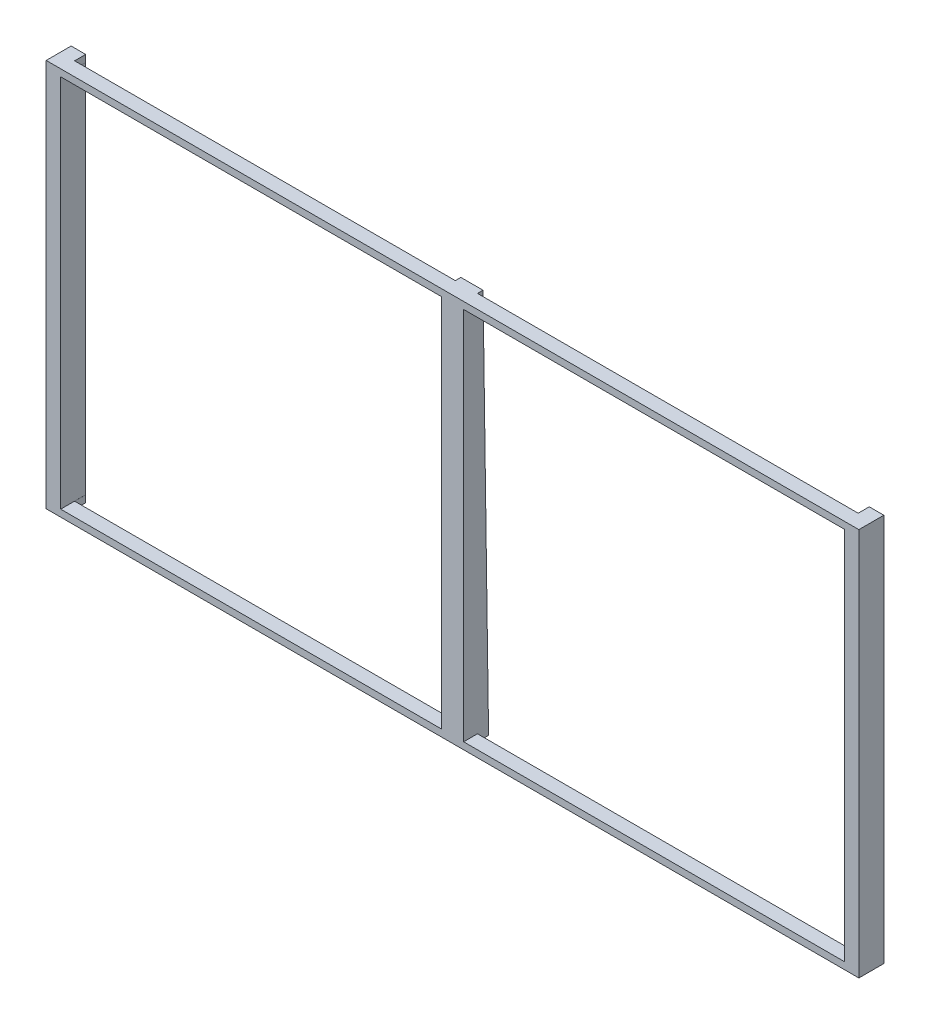
SolidWorks part; units mm, degrees
ref_plane "Спереди" through (0, 0, 0) normal (0, 0, 1) x (1, 0, 0)
ref_plane "Сверху" through (0, 0, 0) normal (0, 1, 0) x (1, 0, 0)
ref_plane "Справа" through (0, 0, 0) normal (1, 0, 0) x (0, 0, -1)
sketch "Эскиз1" plane through (0, 0, 0) normal (0, 0, 1) x (1, 0, 0)
  line L1 (-2930, 1400) -> (2930, 1400)
  line L2 (-2930, 1400) -> (-2930, -1400)
  line L3 (-2930, -1400) -> (2930, -1400)
  line L4 (2930, 1400) -> (2930, -1400)
  line L5 (-2930, 1400) -> (2930, -1400) construction
  line L6 (-2930, -1400) -> (2930, 1400) construction
  line L7 (-2825.3571, 1350) -> (-80, 1350)
  line L8 (-2825.3571, 1350) -> (-2825.3571, -1350)
  line L9 (-2825.3571, -1350) -> (-80, -1350)
  line L10 (-80, 1350) -> (-80, -1350)
  line L11 (80, 1350) -> (2825.3571, 1350)
  line L12 (80, 1350) -> (80, -1350)
  line L13 (80, -1350) -> (2825.3571, -1350)
  line L14 (2825.3571, 1350) -> (2825.3571, -1350)
  point P0 (0, 0)
extrude "Бобышка-Вытянуть1" add sketch "Эскиз1" along normal blind 180
sketch "Эскиз2" plane through (0, -1400, 0) normal (0, -1, 0) x (1, 0, 0)
  line L2 (-2825, 80) -> (-80, 80)
  line L3 (-2825, 80) -> (-2825, 0)
  line L4 (-2825, 0) -> (-80, 0)
  line L5 (-80, 80) -> (-80, 0)
  line L6 (-2825, 80) -> (-80, 0) construction
  line L7 (-2825, 0) -> (-80, 80) construction
  line L8 (0, 424.0898) -> (0, -233.7336) construction
  line L9 (2825, 0) -> (80, 80) construction
  line L10 (2825, 80) -> (80, 0) construction
  line L11 (80, 80) -> (80, 0)
  line L12 (2825, 0) -> (80, 0)
  line L13 (2825, 80) -> (2825, 0)
  line L14 (2825, 80) -> (80, 80)
  line L15 (-2930, 0) -> (2930, 0) construction
  point P2 (-1452.5, 40)
  point P15 (1452.5, 40)
extrude "Вырез-Вытянуть1" cut sketch "Эскиз2" against normal through all
sketch "Эскиз3" plane through (-80, 0, 0) normal (-1, 0, 0) x (0, 0, 1)
  line L0 (0, 1400) -> (0, -1400)
  line L1 (0, 1400) -> (80, 1400) construction
  line L2 (0, -1400) -> (0, 1400) construction
  line L3 (0, -1400) -> (40, 1400)
  line L4 (40, 1400) -> (0, 1400)
extrude "Вырез-Вытянуть2" cut sketch "Эскиз3" against normal up to surface (160 mm away) up to face at (80, 0, 85)
